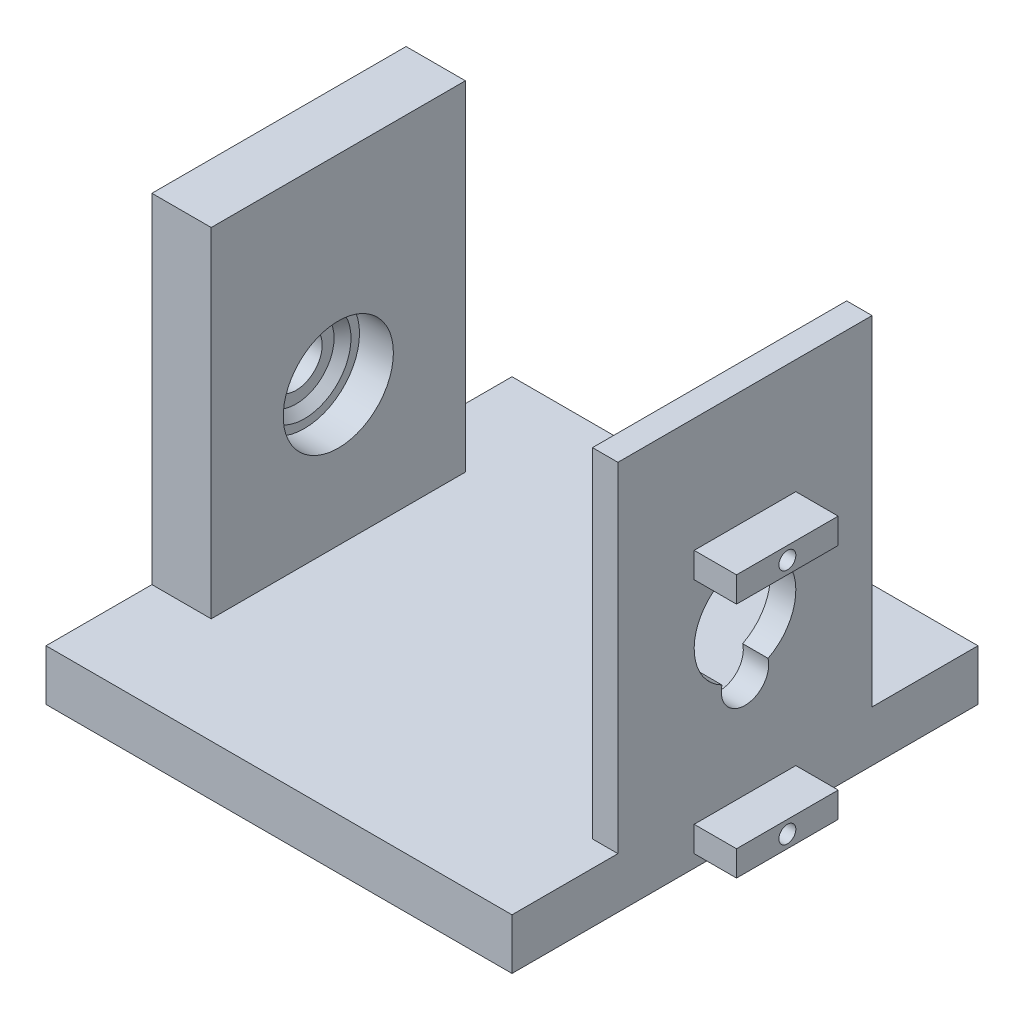
SolidWorks part; units mm, degrees
ref_plane "Alzado" through (0, 0, 0) normal (0, 0, 1) x (1, 0, 0)
ref_plane "Planta" through (0, 0, 0) normal (0, 1, 0) x (1, 0, 0)
ref_plane "Vista lateral" through (0, 0, 0) normal (1, 0, 0) x (0, 0, -1)
sketch "Croquis8" plane through (0, 0, 0) normal (0, 1, 0) x (1, 0, 0)
  line L1 (-27.5, -27.5) -> (27.5, -27.5)
  line L2 (-27.5, -27.5) -> (-27.5, 27.5)
  line L3 (-27.5, 27.5) -> (27.5, 27.5)
  line L4 (27.5, -27.5) -> (27.5, 27.5)
  line L5 (-27.5, -27.5) -> (27.5, 27.5) construction
  line L6 (-27.5, 27.5) -> (27.5, -27.5) construction
  circle A0 centre (0, 0) radius 22
  dimension "D1" = 44
  dimension "D2" = 55
  dimension "D3" = 55
extrude "Saliente-Extruir4" add sketch "Croquis8" along normal blind 6 contours L1 L4 L3 L2 A0 | A0 region at (-26.7222, 0, 0) region at (0, 0, 0)
extrude "Cortar-Extruir6" cut sketch "Croquis8<3>" along normal blind 3 contours A0 region at (0, 0, 0)
sketch "Croquis8<3>" plane through (0, 0, 0) normal (0, 1, 0) x (1, 0, 0) same geometry as "Croquis8"
fillet "Redondeo1" radius 0.5 1 edges at (0, 3, 22)
sketch "Croquis9" plane through (0, 6, 0) normal (0, 1, 0) x (1, 0, 0)
  line L0 (-27.5, -27.5) -> (-27.5, 27.5) construction
  line L1 (-27.5, 15) -> (-20.5, 15)
  line L2 (-27.5, 15) -> (-27.5, -15)
  line L3 (-27.5, -15) -> (-20.5, -15)
  line L4 (-20.5, 15) -> (-20.5, -15)
  line L5 (27.5, -27.5) -> (27.5, 27.5) construction
  line L6 (27.5, 15) -> (24.5, 15)
  line L7 (27.5, 15) -> (27.5, -15)
  line L8 (27.5, -15) -> (24.5, -15)
  line L9 (24.5, 15) -> (24.5, -15)
  point P12 (-20.5, 0)
  point P14 (24.5, 0)
  dimension "D1" = 7
  dimension "D2" = 3
  dimension "D3" = 30
  dimension "D4" = 30
extrude "Saliente-Extruir5" add sketch "Croquis9" along normal blind 40
sketch "Croquis10" plane through (27.5, 0, 0) normal (1, 0, 0) x (0, 0, -1)
  line L0 (0, 0) -> (0, 46) construction
  line L1 (-27.5, 0) -> (27.5, 0) construction
  line L2 (-15, 46) -> (15, 46) construction
  line L4 (-6, 32.5) -> (6, 32.5)
  line L5 (-6, 32.5) -> (-6, 29.5)
  line L6 (-6, 29.5) -> (6, 29.5)
  line L7 (6, 32.5) -> (6, 29.5)
  line L8 (-6, 4.5) -> (6, 4.5)
  line L9 (-6, 4.5) -> (-6, 1.5)
  line L10 (-6, 1.5) -> (6, 1.5)
  line L11 (6, 4.5) -> (6, 1.5)
  circle A0 centre (0, 22.45) radius 6
  circle A1 centre (0, 16.45) radius 2.8
  circle A2 centre (0, 31) radius 1
  circle A3 centre (0, 3) radius 1
  point P22 (0, 4.5)
  point P23 (0, 29.5)
  point P24 (6, 3)
  point P25 (6, 31)
  dimension "D1" = 12
  dimension "D2" = 5.6
  dimension "D3" = 2
  dimension "D9" = 2
  dimension "D4" = 3
  dimension "D5" = 8.55
  dimension "D6" = 19.45
  dimension "D7" = 3
  dimension "D8" = 12
extrude "Saliente-Extruir6" add sketch "Croquis10" along normal blind 5 contours L0 L10 L11 L8 A3 | L10 L0 A3 L8 L9 | L6 L0 A2 L4 L5 | L0 L6 L7 L4 A2 region at (27.5, 3, 3.2463) region at (27.5, 31, 3.2463) region at (27.5, 31, -3.2463) region at (27.5, 3, -3.2463)
extrude "Cortar-Extruir7" cut sketch "Croquis10<3>" against normal blind 5 contours A1 L0 A0 | A0 L0 A1 | L0 A0 A1 | L0 A1 A0 | A1 L0 A0 | L0 A1 A0 region at (27.5, 15.3871, 1.2699) region at (27.5, 15.3871, -1.2699) region at (27.5, 17.748, 1.0888) region at (27.5, 17.748, -1.0888) region at (27.5, 22.9611, 2.7049) region at (27.5, 22.9611, -2.7049)
sketch "Croquis10<3>" plane through (27.5, 0, 0) normal (1, 0, 0) x (0, 0, -1) same geometry as "Croquis10"
sketch "Croquis11" plane through (-20.5, 0, 0) normal (1, 0, 0) x (0, 0, -1)
  circle A0 centre (0, 22.45) radius 3.1
  circle A1 centre (0, 22.45) radius 6.5
  dimension "D1" = 6.2
  dimension "D2" = 13
extrude "Cortar-Extruir8" cut sketch "Croquis11" against normal up to next contours A0 region at (-20.5, 22.45, 0)
extrude "Cortar-Extruir9" cut sketch "Croquis11<3>" against normal offset from surface (4 mm away) 3 contours A1 up to face at (-27.5, 22.45, 3.1)
sketch "Croquis11<3>" plane through (-20.5, 0, 0) normal (1, 0, 0) x (0, 0, -1) same geometry as "Croquis11"
sketch "Croquis12" plane through (-24.5, 0, 0) normal (1, 0, 0) x (0, 0, -1)
  circle A0 centre (0, 22.45) radius 5.5
  circle M3 centre (0, 22.45) radius 3.1
  dimension "D1" = 11
extrude "Cortar-Extruir10" cut sketch "Croquis12" against normal blind 1 contours A0 M3 region at (-24.5, 22.45, 5.3444)
chamfer "Chaflán1" distance 1 angle 45 1 edges at (-25.5, 22.45, -5.5)
